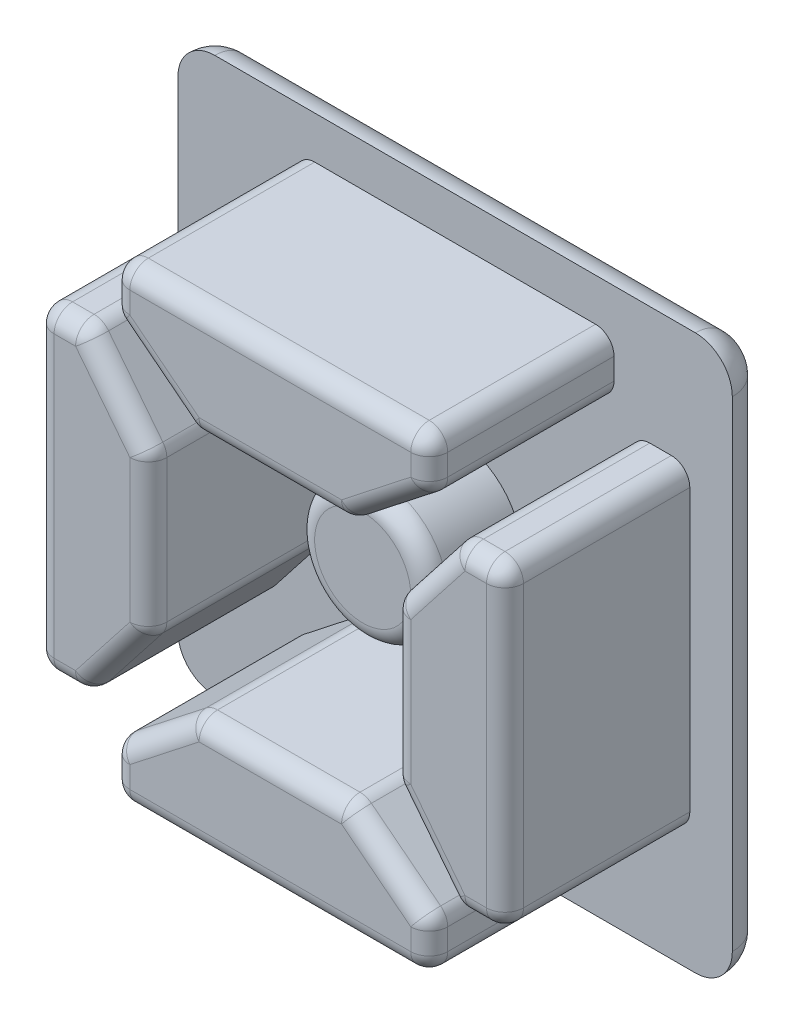
SolidWorks part; units mm, degrees
ref_plane "Plan de face" through (0, 0, 0) normal (0, 0, 1) x (1, 0, 0)
ref_plane "Plan de dessus" through (0, 0, 0) normal (0, 1, 0) x (1, 0, 0)
ref_plane "Plan de droite" through (0, 0, 0) normal (1, 0, 0) x (0, 0, -1)
sketch "Esquisse1" plane through (0, 0, 0) normal (0, 0, 1) x (1, 0, 0)
  line L1 (0, 0) -> (30, 0)
  line L2 (0, 0) -> (0, 30)
  line L3 (0, 30) -> (30, 30)
  line L4 (30, 0) -> (30, 30)
  dimension "D1" = 30
  dimension "D2" = 30
extrude "Boss.-Extru.1" add sketch "Esquisse1" along normal blind 2
sketch "Esquisse5" plane through (0, 0, 2) normal (0, 0, 1) x (1, 0, 0)
  line L0 (27.7, 6.4) -> (27.7, 23.6)
  line L1 (27.7, 23.6) -> (25.05, 23.6)
  line L2 (25.05, 23.6) -> (21.6, 19.2)
  line L3 (21.6, 19.2) -> (21.6, 10.8)
  line L4 (21.6, 10.8) -> (25.05, 6.4)
  line L5 (25.05, 6.4) -> (27.7, 6.4)
  line L6 (0, 0) -> (30, 0) construction
  line L8 (30, 0) -> (30, 30) construction
  dimension "D5" = 2.3
  dimension "D1" = 17.2
  dimension "D2" = 6.1
  dimension "D3" = 8.4
  dimension "D4" = 4.4
  dimension "D6" = 6.4
  dimension "D7" = 2.65
  dimension "D8" = 2.65
extrude "Boss.-Extru.5" add sketch "Esquisse5" along normal blind 10
fillet "Congé1" radius 1 6 edges at (27.7, 6.4, 7) (27.7, 23.6, 7) (25.05, 6.4, 7) (21.6, 10.8, 7) (21.6, 19.2, 7) (25.05, 23.6, 7)
sketch "Esquisse2" plane through (0, 0, 2) normal (0, 0, 1) x (1, 0, 0)
  line L0 (0, 0) -> (30, 0) construction
  line L1 (0, 30) -> (0, 0) construction
  circle A0 centre (15, 15) radius 3.6
  dimension "D1" = 15
  dimension "D2" = 15
extrude "Boss.-Extru.6" add sketch "Esquisse2" along normal blind 5
pattern_circular "Répétition circulaire1" count 4 over 360 about axis through (15, 15, 7) along (0, 0, 1) of "Congé1", "Boss.-Extru.5"
fillet "Congé2" radius 2 4 edges at (30, 0, 1) (0, 0, 1) (30, 30, 1) (0, 30, 1)
fillet "Congé3" radius 1 49 edges at (18.6, 15, 7) (6.5008, 4.9009, 12) (8.6556, 6.7186, 12) (10.8189, 8.3452, 12) (15, 8.4, 12) (19.1811, 8.3452, 12) (21.3444, 6.7186, 12) (23.4992, 4.9009, 12) (23.6, 3.8817, 12) (23.3071, 2.5929, 12) (15, 2.3, 12) (6.6929, 2.5929, 12) (6.4, 3.8817, 12) (25.0991, 6.5008, 12) (23.2814, 8.6556, 12) (21.6548, 10.8189, 12) (21.6, 15, 12) (21.6548, 19.1811, 12) (23.2814, 21.3444, 12) (25.0991, 23.4992, 12) (26.1183, 23.6, 12) (27.4071, 23.3071, 12) (27.7, 15, 12) (27.4071, 6.6929, 12) (26.1183, 6.4, 12) (23.4992, 25.0991, 12) (21.3444, 23.2814, 12) (19.1811, 21.6548, 12) (15, 21.6, 12) (10.8189, 21.6548, 12) (8.6556, 23.2814, 12) (6.5008, 25.0991, 12) (6.4, 26.1183, 12) (6.6929, 27.4071, 12) (15, 27.7, 12) (23.3071, 27.4071, 12) (23.6, 26.1183, 12) (4.9009, 23.4992, 12) (6.7186, 21.3444, 12) (8.3452, 19.1811, 12) (8.4, 15, 12) (8.3452, 10.8189, 12) (6.7186, 8.6556, 12) (4.9009, 6.5008, 12) (3.8817, 6.4, 12) (2.5929, 6.6929, 12) (2.3, 15, 12) (2.5929, 23.3071, 12) (3.8817, 23.6, 12)
fillet "Congé4" radius 2 8 edges at (29.4142, 29.4142, 0) (15, 30, 0) (0.5858, 29.4142, 0) (0, 15, 0) (0.5858, 0.5858, 0) (15, 0, 0) (29.4142, 0.5858, 0) (30, 15, 0)
